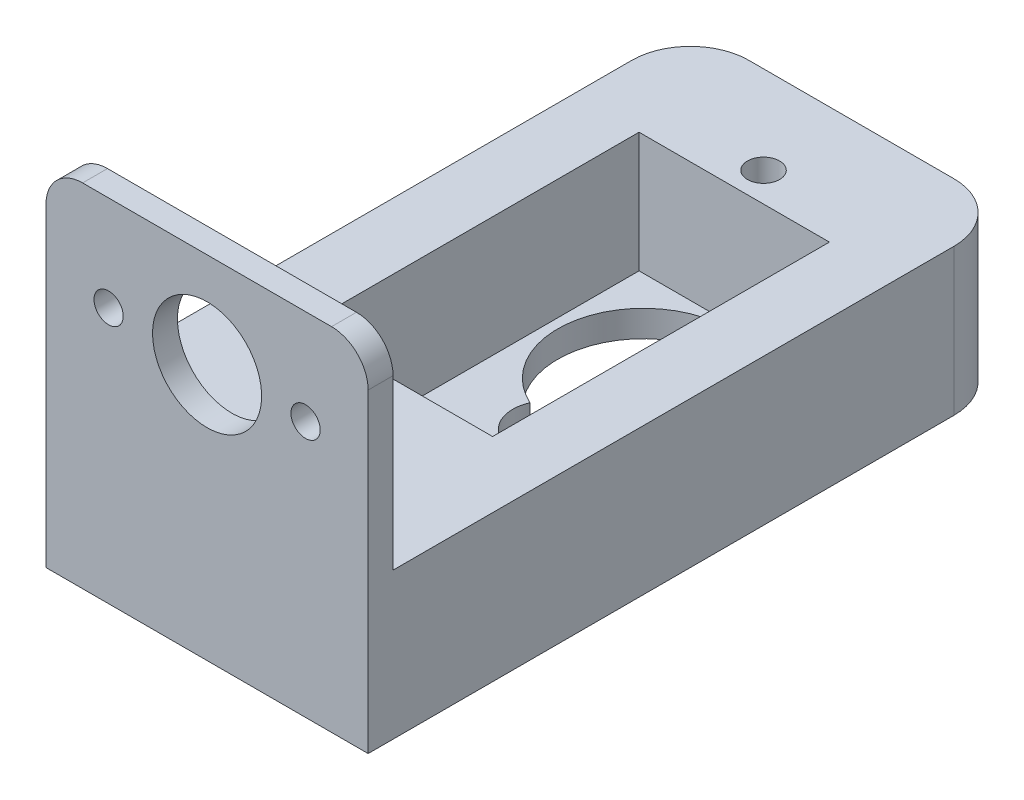
SolidWorks part; units mm, degrees
ref_plane "Front Plane" through (0, 0, 0) normal (0, 0, 1) x (1, 0, 0)
ref_plane "Top Plane" through (0, 0, 0) normal (0, 1, 0) x (1, 0, 0)
ref_plane "Right Plane" through (0, 0, 0) normal (1, 0, 0) x (0, 0, -1)
sketch "Sketch1" plane through (0, 0, 0) normal (0, 1, 0) x (1, 0, 0)
  line L1 (0, 0) -> (22, 0)
  line L2 (0, 0) -> (0, 44)
  line L3 (0, 44) -> (22, 44)
  line L4 (22, 0) -> (22, 44)
  dimension "D1" = 22
  dimension "D2" = 44
extrude "Boss-Extrude1" add sketch "Sketch1" along normal blind 10 contours L2 L3 L4 L1
sketch "Sketch2" plane through (0, 10, 0) normal (0, 1, 0) x (1, 0, 0)
  line L0 (0, 0) -> (0, 44) construction
  line L1 (4.5, 36) -> (17.5, 36)
  line L2 (4.5, 36) -> (4.5, 13)
  line L3 (4.5, 13) -> (17.5, 13)
  line L4 (17.5, 36) -> (17.5, 13)
  line L5 (0, 0) -> (22, 0) construction
  dimension "D1" = 13
  dimension "D2" = 23
  dimension "D3" = 4.5
  dimension "D4" = 13
extrude "Cut-Extrude1" cut sketch "Sketch2" against normal blind 8.2
sketch "Sketch3" plane through (0, 1.8, 0) normal (0, 1, 0) x (1, 0, 0)
  line L0 (17.5, 36) -> (4.5, 36) construction
  line L1 (17.5, 13) -> (17.5, 36) construction
  circle A0 centre (11, 29.8) radius 5.85
  dimension "D1" = 6.2
  dimension "D3" = 11.7
  dimension "D2" = 6.5
extrude "Cut-Extrude2" cut sketch "Sketch3" against normal through all
sketch "Sketch4" plane through (0, 10, 0) normal (0, 1, 0) x (1, 0, 0)
  line L0 (0, 0) -> (0, 44) construction
  line L1 (0, 1.7) -> (22, 1.7)
  line L2 (0, 1.7) -> (0, 0)
  line L3 (0, 0) -> (22, 0)
  line L4 (22, 1.7) -> (22, 0)
  dimension "D1" = 1.7
extrude "Boss-Extrude2" add sketch "Sketch4" along normal blind 14
sketch "Sketch5" plane through (0, 0, -1.7) normal (0, 0, -1) x (-1, 0, 0)
  line L0 (-22, 24) -> (-22, 10) construction
  line L1 (-22, 10) -> (0, 10) construction
  circle A0 centre (-11, 17.5) radius 3.725
  circle A3 centre (-17.725, 17.5) radius 1
  circle A4 centre (-4.275, 17.5) radius 1
  dimension "D1" = 7.45
  dimension "D2" = 3
  dimension "D5" = 7.5
  dimension "D3" = 3
  dimension "D4" = 11
extrude "Cut-Extrude3" cut sketch "Sketch5" against normal through all contours A0
extrude "Cut-Extrude4" cut sketch "Sketch5<3>" against normal blind 10
sketch "Sketch5<3>" plane through (0, 0, -1.7) normal (0, 0, -1) x (-1, 0, 0) same geometry as "Sketch5"
sketch "Sketch6" plane through (0, 10, 0) normal (0, 1, 0) x (1, 0, 0)
  line L0 (17.5, 36) -> (4.5, 36) construction
  line L1 (4.5, 13) -> (17.5, 13) construction
  circle A0 centre (11, 38) radius 1.1
  circle A1 centre (11, 10) radius 1.1
  point P8 (0, 0)
  dimension "D1" = 2
  dimension "D2" = 2.2
  dimension "D4" = 2.2
  dimension "D3" = 3
extrude "Cut-Extrude5" cut sketch "Sketch6" against normal blind 4
fillet "Fillet1" radius 4 2 edges at (0, 5, -44) (22, 5, -44)
fillet "Fillet2" radius 2.5 2 edges at (0, 24, -0.85) (22, 24, -0.85)
sketch "Sketch7" plane through (0, 1.8, 0) normal (0, 1, 0) x (1, 0, 0)
  arc A0 (8.5739, 24.4768) -> (12.9671, 24.4768) centre (10.7705, 23.5098) ccw
  circle A1 centre (11, 29.8) radius 5.85 construction
  arc A2 (8.5739, 24.4768) -> (12.9671, 24.4768) centre (10.7705, 29.8856) ccw
  point P4 (11.0804, 23.3353)
  point P5 (13.1003, 24.34)
  point P8 (8.5739, 24.4768)
  point P9 (13.0421, 24.318)
  point P10 (12.9671, 24.4768)
extrude "Cut-Extrude6" cut sketch "Sketch7" against normal blind 10
